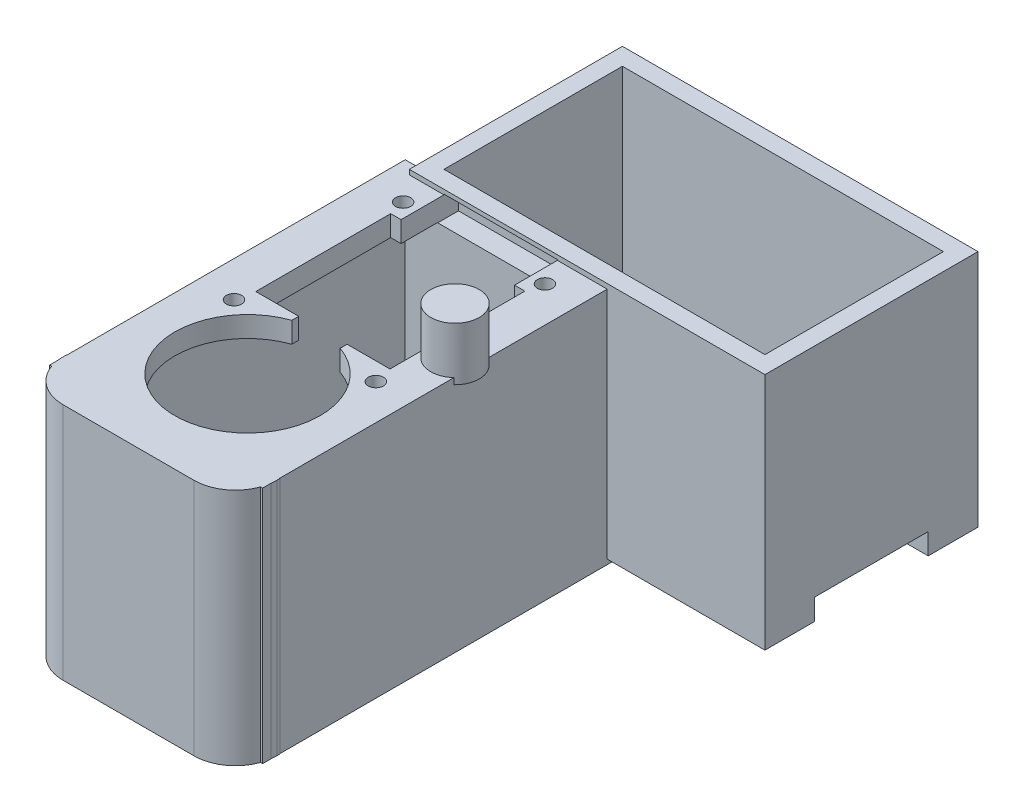
SolidWorks part; units mm, degrees
ref_plane "Front Plane" through (0, 0, 0) normal (0, 0, 1) x (1, 0, 0)
ref_plane "Top Plane" through (0, 0, 0) normal (0, 1, 0) x (1, 0, 0)
ref_plane "Right Plane" through (0, 0, 0) normal (1, 0, 0) x (0, 0, -1)
ref_plane "PZ_m38_200" through (0, 0, -38.2) normal (0, 0, 1) x (1, 0, 0)
sketch "S_box1" plane through (0, 0, -38.2) normal (0, 0, 1) x (1, 0, 0)
  line L0 (-15.4, 2.9) -> (15.4, 2.9)
  line L1 (15.4, 2.9) -> (15.4, 37.4)
  line L2 (15.4, 37.4) -> (-15.4, 37.4)
  line L3 (-15.4, 37.4) -> (-15.4, 2.9)
  dimension "P1" = 15.4
  dimension "P2" = 2.9
  dimension "P3" = 15.4
  dimension "P4" = 2.9
  dimension "P5" = 15.4
  dimension "P6" = 37.4
  dimension "P7" = 15.4
  dimension "P8" = 37.4
extrude "Boss_1" add sketch "S_box1" along normal blind 2.5
ref_plane "PZ_p10_700" through (0, 0, 10.7) normal (0, 0, 1) x (1, 0, 0)
sketch "S_box2" plane through (0, 0, 10.7) normal (0, 0, 1) x (1, 0, 0)
  line L0 (-15.4, 2.9) -> (15.4, 2.9)
  line L1 (15.4, 2.9) -> (15.4, 37.4)
  line L2 (15.4, 37.4) -> (-15.4, 37.4)
  line L3 (-15.4, 37.4) -> (-15.4, 2.9)
  dimension "P1" = 15.4
  dimension "P2" = 2.9
  dimension "P3" = 15.4
  dimension "P4" = 2.9
  dimension "P5" = 15.4
  dimension "P6" = 37.4
  dimension "P7" = 15.4
  dimension "P8" = 37.4
extrude "Boss_2" add sketch "S_box2" along normal blind 2.5
sketch "S_box3" plane through (0, 0, -38.2) normal (0, 0, 1) x (1, 0, 0)
  line L0 (-15.4, 2.9) -> (-12.9, 2.9)
  line L1 (-12.9, 2.9) -> (-12.9, 37.4)
  line L2 (-12.9, 37.4) -> (-15.4, 37.4)
  line L3 (-15.4, 37.4) -> (-15.4, 2.9)
  dimension "P1" = 15.4
  dimension "P2" = 2.9
  dimension "P3" = 12.9
  dimension "P4" = 2.9
  dimension "P5" = 12.9
  dimension "P6" = 37.4
  dimension "P7" = 15.4
  dimension "P8" = 37.4
extrude "Boss_3" add sketch "S_box3" along normal blind 51.4
sketch "S_box4" plane through (0, 0, -38.2) normal (0, 0, 1) x (1, 0, 0)
  line L0 (12.9, 2.9) -> (15.4, 2.9)
  line L1 (15.4, 2.9) -> (15.4, 37.4)
  line L2 (15.4, 37.4) -> (12.9, 37.4)
  line L3 (12.9, 37.4) -> (12.9, 2.9)
  dimension "P1" = 12.9
  dimension "P2" = 2.9
  dimension "P3" = 15.4
  dimension "P4" = 2.9
  dimension "P5" = 15.4
  dimension "P6" = 37.4
  dimension "P7" = 12.9
  dimension "P8" = 37.4
extrude "Boss_4" add sketch "S_box4" along normal blind 51.4
sketch "S_box5" plane through (0, 0, -38.2) normal (0, 0, 1) x (1, 0, 0)
  line L0 (-15.4, 34.4) -> (15.4, 34.4)
  line L1 (15.4, 34.4) -> (15.4, 37.4)
  line L2 (15.4, 37.4) -> (-15.4, 37.4)
  line L3 (-15.4, 37.4) -> (-15.4, 34.4)
  dimension "P1" = 15.4
  dimension "P2" = 34.4
  dimension "P3" = 15.4
  dimension "P4" = 34.4
  dimension "P5" = 15.4
  dimension "P6" = 37.4
  dimension "P7" = 15.4
  dimension "P8" = 37.4
extrude "Boss_5" add sketch "S_box5" along normal blind 51.4
ref_plane "PZ_m67_400" through (0, 0, -67.4) normal (0, 0, 1) x (1, 0, 0)
sketch "S_box6" plane through (0, 0, -67.4) normal (0, 0, 1) x (1, 0, 0)
  line L0 (-13.2, 3.6) -> (-10.7, 3.6)
  line L1 (-10.7, 3.6) -> (-10.7, 38.1)
  line L2 (-10.7, 38.1) -> (-13.2, 38.1)
  line L3 (-13.2, 38.1) -> (-13.2, 3.6)
  dimension "P1" = 13.2
  dimension "P2" = 3.6
  dimension "P3" = 10.7
  dimension "P4" = 3.6
  dimension "P5" = 10.7
  dimension "P6" = 38.1
  dimension "P7" = 13.2
  dimension "P8" = 38.1
extrude "Boss_6" add sketch "S_box6" along normal blind 30.8
sketch "S_box7" plane through (0, 0, -67.4) normal (0, 0, 1) x (1, 0, 0)
  line L0 (35.7, 3.6) -> (38.2, 3.6)
  line L1 (38.2, 3.6) -> (38.2, 38.1)
  line L2 (38.2, 38.1) -> (35.7, 38.1)
  line L3 (35.7, 38.1) -> (35.7, 3.6)
  dimension "P1" = 35.7
  dimension "P2" = 3.6
  dimension "P3" = 38.2
  dimension "P4" = 3.6
  dimension "P5" = 38.2
  dimension "P6" = 38.1
  dimension "P7" = 35.7
  dimension "P8" = 38.1
extrude "Boss_7" add sketch "S_box7" along normal blind 30.8
sketch "S_box8" plane through (0, 0, -67.4) normal (0, 0, 1) x (1, 0, 0)
  line L0 (-13.2, 3.6) -> (38.2, 3.6)
  line L1 (38.2, 3.6) -> (38.2, 38.1)
  line L2 (38.2, 38.1) -> (-13.2, 38.1)
  line L3 (-13.2, 38.1) -> (-13.2, 3.6)
  dimension "P1" = 13.2
  dimension "P2" = 3.6
  dimension "P3" = 38.2
  dimension "P4" = 3.6
  dimension "P5" = 38.2
  dimension "P6" = 38.1
  dimension "P7" = 13.2
  dimension "P8" = 38.1
extrude "Boss_8" add sketch "S_box8" along normal blind 2.5
ref_plane "PZ_m39_100" through (0, 0, -39.1) normal (0, 0, 1) x (1, 0, 0)
sketch "S_box9" plane through (0, 0, -39.1) normal (0, 0, 1) x (1, 0, 0)
  line L0 (-13.2, 3.6) -> (38.2, 3.6)
  line L1 (38.2, 3.6) -> (38.2, 38.1)
  line L2 (38.2, 38.1) -> (-13.2, 38.1)
  line L3 (-13.2, 38.1) -> (-13.2, 3.6)
  dimension "P1" = 13.2
  dimension "P2" = 3.6
  dimension "P3" = 38.2
  dimension "P4" = 3.6
  dimension "P5" = 38.2
  dimension "P6" = 38.1
  dimension "P7" = 13.2
  dimension "P8" = 38.1
extrude "Boss_9" add sketch "S_box9" along normal blind 2.5
sketch "S_box10" plane through (0, 0, -67.4) normal (0, 0, 1) x (1, 0, 0)
  line L0 (-13.2, 3.6) -> (38.2, 3.6)
  line L1 (38.2, 3.6) -> (38.2, 6.6)
  line L2 (38.2, 6.6) -> (-13.2, 6.6)
  line L3 (-13.2, 6.6) -> (-13.2, 3.6)
  dimension "P1" = 13.2
  dimension "P2" = 3.6
  dimension "P3" = 38.2
  dimension "P4" = 3.6
  dimension "P5" = 38.2
  dimension "P6" = 6.6
  dimension "P7" = 13.2
  dimension "P8" = 6.6
extrude "Boss_10" add sketch "S_box10" along normal blind 30.8
ref_plane "PY_p2_900" through (0, 2.9, 0) normal (0, 1, 0) x (1, 0, 0)
sketch "S_prism11" plane through (0, 2.9, 0) normal (0, 1, 0) x (1, 0, 0)
  line L0 (-15.45, -10.75) -> (15.45, -10.75)
  line L1 (15.45, -10.75) -> (15.45, -11.2)
  line L2 (9.45, -17.2) -> (-9.45, -17.2)
  line L3 (-15.45, -11.2) -> (-15.45, -10.75)
  arc A0 (15.45, -11.2) -> (9.45, -17.2) centre (9.4499, -11.1999) cw
  arc A1 (-9.45, -17.2) -> (-15.45, -11.2) centre (-9.4499, -11.1999) cw
extrude "Boss_11" add sketch "S_prism11" along normal blind 34.5
ref_plane "PY_p36_500" through (0, 36.5, 0) normal (0, 1, 0) x (1, 0, 0)
sketch "S_cyl12" plane through (0, 36.5, 0) normal (0, 1, 0) x (1, 0, 0)
  circle A0 centre (13, 17) radius 3.5
  dimension "D1_S_cyl12" = 7
  dimension "P2" = 13
  dimension "P3" = 17
extrude "Boss_12" add sketch "S_cyl12" along normal blind 7.7
ref_plane "PY_p34_300" through (0, 34.3, 0) normal (0, 1, 0) x (1, 0, 0)
sketch "S_hole13" plane through (0, 34.3, 0) normal (0, 1, 0) x (1, 0, 0)
  circle A0 centre (0, 0) radius 10.5
  dimension "D1_S_hole13" = 21
extrude "Hole_13" cut sketch "S_hole13" along normal blind 3.2
ref_plane "PZ_m30_400" through (0, 0, -30.4) normal (0, 0, 1) x (1, 0, 0)
sketch "S_cut14" plane through (0, 0, -30.4) normal (0, 0, 1) x (1, 0, 0)
  line L0 (-9.7, 34.35) -> (9.7, 34.35)
  line L1 (9.7, 34.35) -> (9.7, 37.5)
  line L2 (9.7, 37.5) -> (-9.7, 37.5)
  line L3 (-9.7, 37.5) -> (-9.7, 34.35)
  dimension "P1" = 9.7
  dimension "P2" = 34.35
  dimension "P3" = 9.7
  dimension "P4" = 34.35
  dimension "P5" = 9.7
  dimension "P6" = 37.5
  dimension "P7" = 9.7
  dimension "P8" = 37.5
extrude "Pocket_14" cut sketch "S_cut14" along normal blind 19.5
ref_plane "PZ_m38_700" through (0, 0, -38.7) normal (0, 0, 1) x (1, 0, 0)
sketch "S_cut15" plane through (0, 0, -38.7) normal (0, 0, 1) x (1, 0, 0)
  line L0 (-8.2, 34.35) -> (8.2, 34.35)
  line L1 (8.2, 34.35) -> (8.2, 37.5)
  line L2 (8.2, 37.5) -> (-8.2, 37.5)
  line L3 (-8.2, 37.5) -> (-8.2, 34.35)
  dimension "P1" = 8.2
  dimension "P2" = 34.35
  dimension "P3" = 8.2
  dimension "P4" = 34.35
  dimension "P5" = 8.2
  dimension "P6" = 37.5
  dimension "P7" = 8.2
  dimension "P8" = 37.5
extrude "Pocket_15" cut sketch "S_cut15" along normal blind 8.3
ref_plane "PZ_m11_000" through (0, 0, -11) normal (0, 0, 1) x (1, 0, 0)
sketch "S_cut16" plane through (0, 0, -11) normal (0, 0, 1) x (1, 0, 0)
  line L0 (-3.5, 34.35) -> (3.5, 34.35)
  line L1 (3.5, 34.35) -> (3.5, 37.5)
  line L2 (3.5, 37.5) -> (-3.5, 37.5)
  line L3 (-3.5, 37.5) -> (-3.5, 34.35)
  dimension "P1" = 3.5
  dimension "P2" = 34.35
  dimension "P3" = 3.5
  dimension "P4" = 34.35
  dimension "P5" = 3.5
  dimension "P6" = 37.5
  dimension "P7" = 3.5
  dimension "P8" = 37.5
extrude "Pocket_16" cut sketch "S_cut16" along normal blind 11
sketch "S_hole17" plane through (0, 34.3, 0) normal (0, 1, 0) x (1, 0, 0)
  circle A0 centre (-10.25, 8.3) radius 1.1
  dimension "D1_S_hole17" = 2.2
  dimension "P2" = 10.25
  dimension "P3" = 8.3
extrude "Hole_17" cut sketch "S_hole17" along normal blind 3.2
sketch "S_hole18" plane through (0, 34.3, 0) normal (0, 1, 0) x (1, 0, 0)
  circle A0 centre (10.25, 8.3) radius 1.1
  dimension "D1_S_hole18" = 2.2
  dimension "P2" = 10.25
  dimension "P3" = 8.3
extrude "Hole_18" cut sketch "S_hole18" along normal blind 3.2
sketch "S_hole19" plane through (0, 34.3, 0) normal (0, 1, 0) x (1, 0, 0)
  circle A0 centre (-10.25, 32.75) radius 1.1
  dimension "D1_S_hole19" = 2.2
  dimension "P2" = 10.25
  dimension "P3" = 32.75
extrude "Hole_19" cut sketch "S_hole19" along normal blind 3.2
sketch "S_hole20" plane through (0, 34.3, 0) normal (0, 1, 0) x (1, 0, 0)
  circle A0 centre (10.25, 32.75) radius 1.1
  dimension "D1_S_hole20" = 2.2
  dimension "P2" = 10.25
  dimension "P3" = 32.75
extrude "Hole_20" cut sketch "S_hole20" along normal blind 3.2
ref_plane "PY_p3_500" through (0, 3.5, 0) normal (0, 1, 0) x (1, 0, 0)
sketch "S_hole21" plane through (0, 3.5, 0) normal (0, 1, 0) x (1, 0, 0)
  circle A0 centre (0, 52) radius 10.5
  dimension "D1_S_hole21" = 21
  dimension "P2" = 52
extrude "Hole_21" cut sketch "S_hole21" along normal blind 3.2
ref_plane "PZ_m61_700" through (0, 0, -61.7) normal (0, 0, 1) x (1, 0, 0)
sketch "S_cut22" plane through (0, 0, -61.7) normal (0, 0, 1) x (1, 0, 0)
  line L0 (10.9, 3.5) -> (30.4, 3.5)
  line L1 (30.4, 3.5) -> (30.4, 6.65)
  line L2 (30.4, 6.65) -> (10.9, 6.65)
  line L3 (10.9, 6.65) -> (10.9, 3.5)
  dimension "P1" = 10.9
  dimension "P2" = 3.5
  dimension "P3" = 30.4
  dimension "P4" = 3.5
  dimension "P5" = 30.4
  dimension "P6" = 6.65
  dimension "P7" = 10.9
  dimension "P8" = 6.65
extrude "Pocket_22" cut sketch "S_cut22" along normal blind 19.4
ref_plane "PZ_m60_200" through (0, 0, -60.2) normal (0, 0, 1) x (1, 0, 0)
sketch "S_cut23" plane through (0, 0, -60.2) normal (0, 0, 1) x (1, 0, 0)
  line L0 (30.4, 3.5) -> (38.7, 3.5)
  line L1 (38.7, 3.5) -> (38.7, 6.65)
  line L2 (38.7, 6.65) -> (30.4, 6.65)
  line L3 (30.4, 6.65) -> (30.4, 3.5)
  dimension "P1" = 30.4
  dimension "P2" = 3.5
  dimension "P3" = 38.7
  dimension "P4" = 3.5
  dimension "P5" = 38.7
  dimension "P6" = 6.65
  dimension "P7" = 30.4
  dimension "P8" = 6.65
extrude "Pocket_23" cut sketch "S_cut23" along normal blind 16.4
ref_plane "PZ_m55_500" through (0, 0, -55.5) normal (0, 0, 1) x (1, 0, 0)
sketch "S_cut24" plane through (0, 0, -55.5) normal (0, 0, 1) x (1, 0, 0)
  line L0 (0, 3.5) -> (11, 3.5)
  line L1 (11, 3.5) -> (11, 6.65)
  line L2 (11, 6.65) -> (0, 6.65)
  line L3 (0, 6.65) -> (0, 3.5)
  dimension "P1" = 3.5
  dimension "P2" = 11
  dimension "P3" = 3.5
  dimension "P4" = 11
  dimension "P5" = 6.65
  dimension "P6" = 6.65
extrude "Pocket_24" cut sketch "S_cut24" along normal blind 7
sketch "S_hole25" plane through (0, 3.5, 0) normal (0, 1, 0) x (1, 0, 0)
  circle A0 centre (8.3, 62.25) radius 1.1
  dimension "D1_S_hole25" = 2.2
  dimension "P2" = 8.3
  dimension "P3" = 62.25
extrude "Hole_25" cut sketch "S_hole25" along normal blind 3.2
sketch "S_hole26" plane through (0, 3.5, 0) normal (0, 1, 0) x (1, 0, 0)
  circle A0 centre (8.3, 41.75) radius 1.1
  dimension "D1_S_hole26" = 2.2
  dimension "P2" = 8.3
  dimension "P3" = 41.75
extrude "Hole_26" cut sketch "S_hole26" along normal blind 3.2
sketch "S_hole27" plane through (0, 3.5, 0) normal (0, 1, 0) x (1, 0, 0)
  circle A0 centre (32.75, 62.25) radius 1.1
  dimension "D1_S_hole27" = 2.2
  dimension "P2" = 32.75
  dimension "P3" = 62.25
extrude "Hole_27" cut sketch "S_hole27" along normal blind 3.2
sketch "S_hole28" plane through (0, 3.5, 0) normal (0, 1, 0) x (1, 0, 0)
  circle A0 centre (32.75, 41.75) radius 1.1
  dimension "D1_S_hole28" = 2.2
  dimension "P2" = 32.75
  dimension "P3" = 41.75
extrude "Hole_28" cut sketch "S_hole28" along normal blind 3.2
equation "\"plate_t\" = 3"
equation "\"clearance\" = 0.5"
